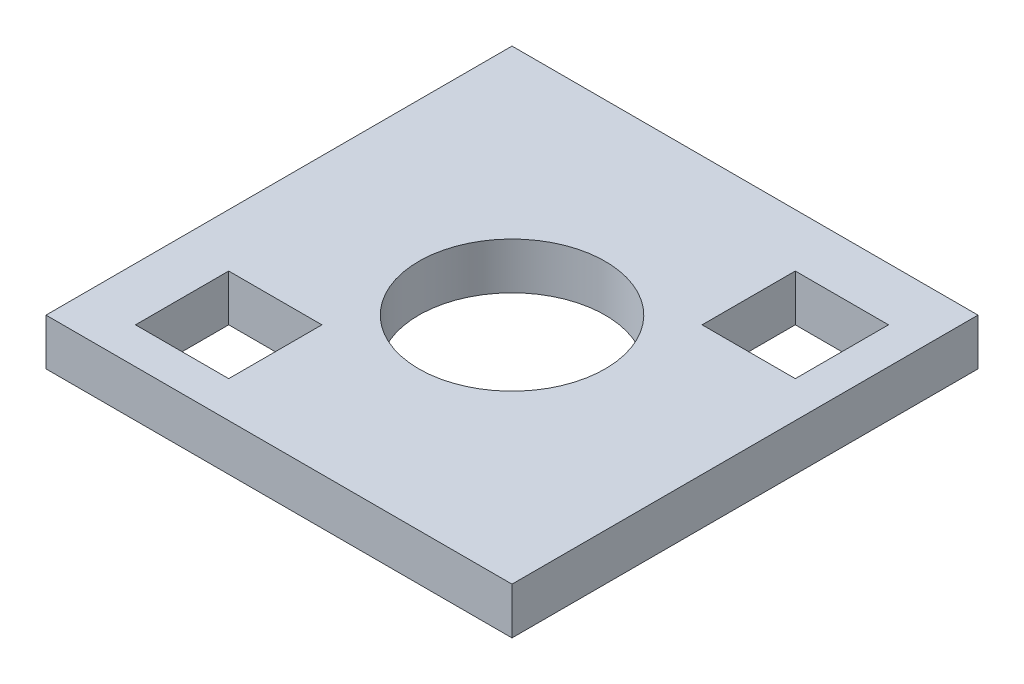
SolidWorks part; units mm, degrees
ref_plane "Front Plane" through (0, 0, 0) normal (0, 0, 1) x (1, 0, 0)
ref_plane "Top Plane" through (0, 0, 0) normal (0, 1, 0) x (1, 0, 0)
ref_plane "Right Plane" through (0, 0, 0) normal (1, 0, 0) x (0, 0, -1)
sketch "Sketch2" plane through (0, 0, 0) normal (0, 1, 0) x (1, 0, 0)
  line L1 (-50, -50) -> (50, -50)
  line L2 (-50, -50) -> (-50, 50)
  line L3 (-50, 50) -> (50, 50)
  line L4 (50, -50) -> (50, 50)
  line L5 (-50, -50) -> (50, 50) construction
  line L6 (-50, 50) -> (50, -50) construction
  circle A0 centre (0, 0) radius 20
  point P0 (0, 0)
  dimension "D2" = 40
  dimension "D1" = 100
extrude "Boss-Extrude3" add sketch "Sketch2" along normal blind 10
sketch "Sketch4" plane through (0, 10, 0) normal (0, 1, 0) x (1, 0, 0)
  line L1 (-38.5873, -42.2049) -> (-18.5873, -42.2049)
  line L2 (-38.5873, -42.2049) -> (-38.5873, -22.2049)
  line L3 (-38.5873, -22.2049) -> (-18.5873, -22.2049)
  line L4 (-18.5873, -42.2049) -> (-18.5873, -22.2049)
  line L5 (-38.5873, -42.2049) -> (-18.5873, -22.2049) construction
  line L6 (-38.5873, -22.2049) -> (-18.5873, -42.2049) construction
  line L7 (22.2049, 38.5873) -> (42.2049, 18.5873) construction
  line L8 (42.2049, 38.5873) -> (22.2049, 18.5873) construction
  line L9 (42.2049, 18.5873) -> (22.2049, 18.5873)
  line L10 (22.2049, 38.5873) -> (22.2049, 18.5873)
  line L11 (42.2049, 38.5873) -> (22.2049, 38.5873)
  line L12 (42.2049, 38.5873) -> (42.2049, 18.5873)
  point P0 (-28.5873, -32.2049)
  point P13 (32.2049, 28.5873)
  dimension "D1" = 20
extrude "Cut-Extrude1" cut sketch "Sketch4" against normal blind 10
